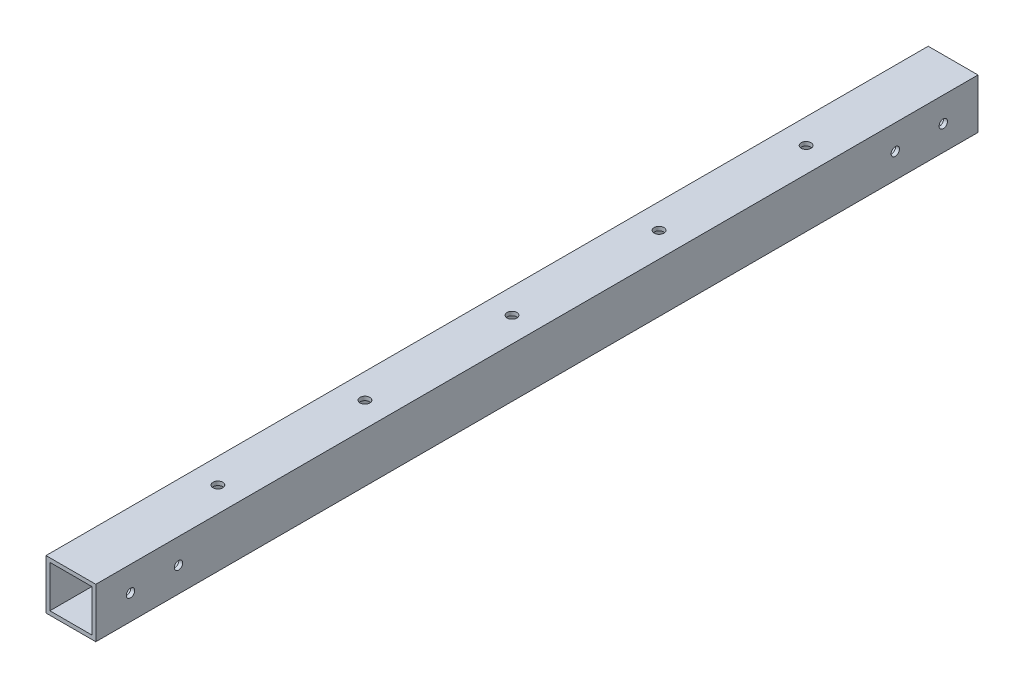
SolidWorks part; units mm, degrees
ref_plane "前基準面" through (0, 0, 0) normal (0, 0, 1) x (1, 0, 0)
ref_plane "上基準面" through (0, 0, 0) normal (0, 1, 0) x (1, 0, 0)
ref_plane "右基準面" through (0, 0, 0) normal (1, 0, 0) x (0, 0, -1)
sketch "草圖1" plane through (0, 0, 0) normal (0, 0, 1) x (1, 0, 0)
  line L0 (-10.7, 10.7) -> (10.7, 10.7)
  line L1 (-12.7, 12.7) -> (12.7, 12.7)
  line L2 (-12.7, 12.7) -> (-12.7, -12.7)
  line L3 (-12.7, -12.7) -> (12.7, -12.7)
  line L4 (12.7, 12.7) -> (12.7, -12.7)
  line L5 (-12.7, 12.7) -> (12.7, -12.7) construction
  line L6 (-12.7, -12.7) -> (12.7, 12.7) construction
  line L7 (10.7, 10.7) -> (10.7, -10.7)
  line L8 (-10.7, -10.7) -> (10.7, -10.7)
  line L9 (-10.7, 10.7) -> (-10.7, -10.7)
  point P0 (0, 0)
  dimension "D1" = 25.4
  dimension "D2" = 25.4
  dimension "D3" = 2
extrude "填料-伸長1" add sketch "草圖1" along normal blind 450 contours L1 L4 L3 L2
extrude "除料-伸長1" cut sketch "草圖1<3>" along normal through all contours L0 L7 L8 L9
sketch "草圖1<3>" plane through (0, 0, 0) normal (0, 0, 1) x (1, 0, 0) same geometry as "草圖1"
sketch "草圖2" plane through (0, -12.7, 0) normal (0, -1, 0) x (1, 0, 0)
  circle A0 centre (0, 17.7) radius 2.15
  circle A1 centre (0, 42.2) radius 2.15
  dimension "D1" = 4.3
  dimension "D2" = 4.3
extrude "除料-伸長2" cut sketch "草圖2" against normal blind 3
sketch "草圖3" plane through (12.7, 0, 0) normal (1, 0, 0) x (0, 0, -1)
  circle A0 centre (-42.2, 0) radius 2.15
  circle A1 centre (-17.7, 0) radius 2.15
extrude "除料-伸長3" cut sketch "草圖3" against normal blind 3 contours A0 | A1
sketch "草圖4" plane through (12.7, 0, 0) normal (1, 0, 0) x (0, 0, -1)
  circle A0 centre (-407.8, 0) radius 2.15
  circle A1 centre (-432.3, 0) radius 2.15
extrude "除料-伸長4" cut sketch "草圖4" against normal blind 3
sketch "草圖5" plane through (0, -12.7, 0) normal (0, -1, 0) x (1, 0, 0)
  circle A0 centre (0, 407.8) radius 2.15
  circle A1 centre (0, 432.3) radius 2.15
extrude "除料-伸長5" cut sketch "草圖5" against normal blind 3
sketch "草圖6" plane through (0, 12.7, 0) normal (0, 1, 0) x (1, 0, 0)
  line L0 (0, -450) -> (0, -375) construction
  line L1 (-12.7, -450) -> (12.7, -450) construction
  line L2 (0, -375) -> (0, -300) construction
  line L3 (0, -300) -> (0, -225) construction
  line L4 (0, -225) -> (0, -150) construction
  line L5 (0, -150) -> (0, -75) construction
  circle A0 centre (0, -375) radius 2.5
  circle A1 centre (0, -300) radius 2.5
  circle A2 centre (0, -225) radius 2.5
  circle A3 centre (0, -150) radius 2.5
  circle A4 centre (0, -75) radius 2.5
  dimension "D6" = 5
  dimension "D7" = 5
  dimension "D8" = 5
  dimension "D9" = 5
  dimension "D10" = 5
  dimension "D1" = 75
  dimension "D2" = 75
  dimension "D3" = 75
  dimension "D4" = 75
  dimension "D5" = 75
extrude "除料-伸長6" cut sketch "草圖6" against normal blind 10
sketch "草圖8" plane through (-12.7, 0, 0) normal (-1, 0, 0) x (0, 0, 1)
  line L0 (450, 0) -> (375, 0) construction
  line L1 (450, 12.7) -> (450, -12.7) construction
  line L2 (375, 0) -> (300, 0) construction
  line L3 (300, 0) -> (225, 0) construction
  line L4 (225, 0) -> (150, 0) construction
  line L5 (150, 0) -> (75, 0) construction
  circle A0 centre (375, 0) radius 2.5
  circle A1 centre (300, 0) radius 2.5
  circle A2 centre (225, 0) radius 2.5
  circle A3 centre (150, 0) radius 2.5
  circle A4 centre (75, 0) radius 2.5
  dimension "D6" = 5
  dimension "D7" = 5
  dimension "D8" = 5
  dimension "D9" = 5
  dimension "D10" = 5
  dimension "D1" = 75
  dimension "D2" = 75
  dimension "D3" = 75
  dimension "D4" = 75
  dimension "D5" = 75
extrude "除料-伸長7" cut sketch "草圖8" against normal blind 10
